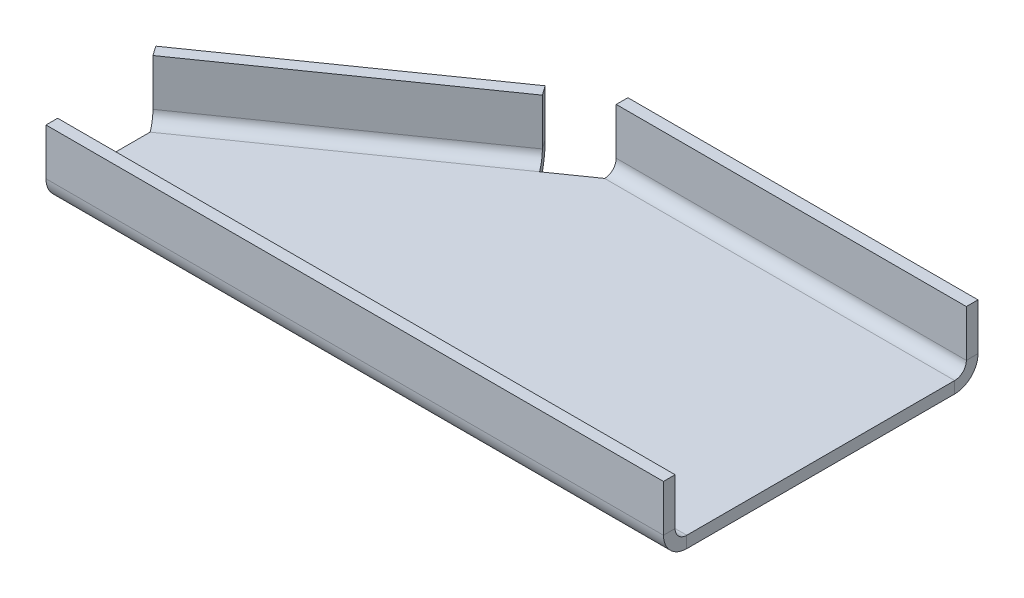
SolidWorks part; units mm, degrees
note: The reader was unsure of these and kept them because the rebuilt part matched: flange length of "Edge-Flange1".
material "5052-H32"
ref_plane "Front" through (0, 0, 0) normal (0, 0, 1) x (1, 0, 0)
ref_plane "Top" through (0, 0, 0) normal (0, 1, 0) x (1, 0, 0)
ref_plane "Right" through (0, 0, 0) normal (1, 0, 0) x (0, 0, -1)
sketch "Sketch1" plane through (0, 0, 0) normal (0, 1, 0) x (1, 0, 0)
  line L0 (0, 0) -> (168.275, 0) construction
  line L1 (168.275, 0) -> (168.275, 85.725) construction
  line L2 (168.275, 85.725) -> (73.025, 85.725) construction
  line L4 (0, 0) -> (0, 34.5923) construction
  line L5 (73.025, 85.725) -> (0, 34.5923) construction
  line L6 (168.275, 79.375) -> (72.8532, 79.375)
  line L7 (72.8532, 79.375) -> (0, 28.3626)
  line L8 (168.275, 79.375) -> (73.025, 79.375) construction
  line L9 (75.952, 81.5448) -> (2.927, 30.4121) construction
  line L13 (0, 6.35) -> (168.275, 6.35)
  line L14 (0, 28.3626) -> (0, 6.35)
  line L15 (168.275, 79.375) -> (168.275, 6.35)
  dimension "D1" = 95.25
  dimension "D2" = 168.275
  dimension "D3" = 85.725
  dimension "D4" = 35
  dimension "D7" = 12.7
  dimension "D5" = 6.35
  dimension "D6" = 5.1031
base flange "Base-Flange1" sketch "Sketch1" thickness 3.175 reverse thickness direction no parameters "D1"=6.35
edge flange "Edge-Flange1" sketch "Sketch12" flange profiles "Sketch12", "Sketch13", "Sketch14" flange angle 90 flange length 19.05 flange position bend outside bend radius 3.175 thickness 3.175 relief rectangular parameters "D6"=10, "D8"=1
sketch "Sketch12" plane through (0, 0, -79.375) normal (0, 0, -1) x (-1, 0, 0)
  line L0 (-168.275, 0) -> (-72.8532, 0) construction
  line L1 (-168.275, 0) -> (-72.8532, 0)
  line L2 (-168.275, 0) -> (-168.275, 15.875)
  line L3 (-168.275, 15.875) -> (-72.8532, 15.875)
  line L4 (-72.8532, 15.875) -> (-72.8532, 0)
sketch "Sketch13" plane through (0, 0, -6.35) normal (0, 0, 1) x (1, 0, 0)
  line L0 (0, 0) -> (168.275, 0) construction
  line L1 (0, 0) -> (168.275, 0)
  line L2 (0, 0) -> (0, 15.875)
  line L3 (0, 15.875) -> (168.275, 15.875)
  line L4 (168.275, 15.875) -> (168.275, 0)
sketch "Sketch14" plane through (-13.3261, 0, -19.0316) normal (-0.5736, 0, -0.8192) x (-0.8192, 0, 0.5736)
  line L0 (-105.2055, 0) -> (-16.2681, 0) construction
  line L1 (-92.4681, 0) -> (-16.2681, 0)
  line L2 (-92.4681, 0) -> (-92.4681, 15.875)
  line L3 (-92.4681, 15.875) -> (-16.2681, 15.875)
  line L4 (-16.2681, 15.875) -> (-16.2681, 0)
  dimension "D1" = 76.2
bend "EdgeBend1" bend radius 3.175 bend angle 90 parameters "D5"=1
bend "EdgeBend2" bend radius 3.175 bend angle 90 parameters "D5"=2
bend "EdgeBend3" bend radius 3.175 bend angle 90 parameters "D5"=3
sketch "Sketch15" plane through (0, 0, 0) normal (0, 0, 1) x (1, 0, 0)
  line L0 (0, -3.175) -> (168.275, -3.175) construction
  line L1 (168.275, 3.175) -> (168.275, 15.875) construction
  circle A0 centre (155.575, 9.525) radius 2.4257
  circle A1 centre (85.725, 9.525) radius 2.4257
  circle A2 centre (15.875, 9.525) radius 2.4257
  dimension "D3" = 4.8514
  dimension "D1" = 12.7
  dimension "D2" = 12.7
  dimension "D4" = 3
  dimension "D5" = 69.85
extrude "Cut-Extrude1" [suppressed] cut sketch "Sketch15" against normal up to surface (3.175 mm away)
sketch "Sketch16" plane through (0, 0, -85.725) normal (0, 0, -1) x (-1, 0, 0)
  line L0 (-120.5641, 15.875) -> (-120.5641, -3.175) construction
  line L1 (-72.8532, 15.875) -> (-168.275, 15.875) construction
  line L2 (-168.275, -3.175) -> (-72.8532, -3.175) construction
  circle A0 centre (-145.9641, 9.525) radius 2.4257
  circle A1 centre (-120.5641, 9.525) radius 2.4257 construction
  circle A2 centre (-95.1641, 9.525) radius 2.4257
  dimension "D2" = 4.8514
  dimension "D1" = 12.7
  dimension "D3" = 25.4
extrude "Cut-Extrude2" [suppressed] cut sketch "Sketch16" against normal up to surface (3.175 mm away)
sketch "Sketch17" plane through (-16.9683, 0, -24.2332) normal (-0.5736, 0, -0.8192) x (-0.8192, 0, 0.5736)
  line L0 (-54.3681, -3.175) -> (-54.3681, 15.875) construction
  line L1 (-16.2681, -3.175) -> (-92.4681, -3.175) construction
  line L2 (-16.2681, 15.875) -> (-92.4681, 15.875) construction
  circle A0 centre (-79.7681, 9.525) radius 2.4257
  circle A1 centre (-28.9681, 9.525) radius 2.4257
  dimension "D1" = 4.8514
  dimension "D2" = 12.7
  dimension "D3" = 25.4
extrude "Cut-Extrude3" [suppressed] cut sketch "Sketch17" against normal up to surface (3.175 mm away)
sketch "Sketch18" plane through (0, 0, 0) normal (0, 1, 0) x (1, 0, 0)
  line L0 (122.2375, 0) -> (122.2375, 35.7505) construction
  line L1 (122.2375, 35.7505) -> (168.275, 35.7505) construction
  line L2 (168.275, 6.35) -> (168.275, 79.375) construction
  line L3 (168.275, 0) -> (0, 0) construction
  circle A0 centre (122.2375, 35.7505) radius 17.4625
  dimension "D3" = 34.925
  dimension "D1" = 46.0375
  dimension "D2" = 35.7505
extrude "Cut-Extrude4" [suppressed] cut sketch "Sketch18" against normal through all
fillet "Fillet1" [suppressed] radius 3.175
sketch "Bend-Lines1" [suppressed] plane through (0, 0, 0) normal (0, 1, 0) x (1, 0, 0)
sketch "Bounding-Box1" [suppressed] plane through (0, 0, 0) normal (0, 1, 0) x (1, 0, 0)
sheet metal parameters "Sheet-Metal1" thickness 3.175 parameters "D1"=6.35
flat pattern "Flat-Pattern1" [suppressed]
sketch "Bend-Lines2" plane through (0, 0, 0) normal (0, 1, 0) x (1, 0, 0)
sketch3d "Bounding-Box2" [suppressed]
  line L0 (-168.275, 6.35, 0) -> (0, 6.35, 0) construction
  line L1 (-168.275, 79.375, 0) -> (0, 79.375, 0) construction
  line L2 (-168.275, 6.35, 0) -> (-168.275, 79.375, 0) construction
  line L3 (0, 6.35, 0) -> (0, 79.375, 0) construction
sheet metal parameters "Sheet-Metal2" thickness 3.175 parameters "D1"=6.35
flat pattern "Flat-Pattern1"
sketch "Bend-Lines2" plane through (0, 0, 0) normal (0, 1, 0) x (1, 0, 0)
  line L0 (60.7745, 74.4182) -> (-1.6448, 30.7117) construction
  line L1 (0, 3.4823) -> (168.275, 3.4823) construction
  line L2 (168.275, 82.2427) -> (72.8532, 82.2427) construction
  line L3 (60.7745, 74.4182) -> (-1.6448, 30.7117) construction
  line L4 (0, 3.4823) -> (168.275, 3.4823) construction
  line L5 (168.275, 82.2427) -> (72.8532, 82.2427) construction
sketch3d "Bounding-Box2" [suppressed]
  line L0 (168.275, -12.0854, 0) -> (-10.5741, -12.0854, 0) construction
  line L1 (168.275, 97.8104, 0) -> (-10.5741, 97.8104, 0) construction
  line L2 (168.275, -12.0854, 0) -> (168.275, 97.8104, 0) construction
  line L3 (-10.5741, -12.0854, 0) -> (-10.5741, 97.8104, 0) construction
bend of the flat pattern "Flatten-<EdgeBend1>1"
bend of the flat pattern "Flatten-<EdgeBend2>1"
bend of the flat pattern "Flatten-<EdgeBend3>1"
sheet metal parameters "Sheet-Metal3" thickness 3.175 parameters "D1"=6.35
flat pattern "Flat-Pattern1"
sketch "Bend-Lines2" plane through (0, 0, 0) normal (0, 1, 0) x (1, 0, 0)
  line L0 (60.7745, 74.4182) -> (-1.6448, 30.7117) construction
  line L1 (0, 3.4823) -> (168.275, 3.4823) construction
  line L2 (168.275, 82.2427) -> (72.8532, 82.2427) construction
  line L3 (60.7745, 74.4182) -> (-1.6448, 30.7117) construction
  line L4 (0, 3.4823) -> (168.275, 3.4823) construction
  line L5 (168.275, 82.2427) -> (72.8532, 82.2427) construction
sketch3d "Bounding-Box2" [suppressed]
  line L0 (168.275, -12.0854, 0) -> (-10.5741, -12.0854, 0) construction
  line L1 (168.275, 97.8104, 0) -> (-10.5741, 97.8104, 0) construction
  line L2 (168.275, -12.0854, 0) -> (168.275, 97.8104, 0) construction
  line L3 (-10.5741, -12.0854, 0) -> (-10.5741, 97.8104, 0) construction
bend of the flat pattern "Flatten-<EdgeBend1>1"
bend of the flat pattern "Flatten-<EdgeBend2>1"
bend of the flat pattern "Flatten-<EdgeBend3>1"
sheet metal parameters "Sheet-Metal4" thickness 3.175 parameters "D1"=6.35
flat pattern "Flat-Pattern1"
sketch "Bend-Lines2" plane through (0, 0, 0) normal (0, 1, 0) x (1, 0, 0)
  line L0 (60.7745, 74.4182) -> (-1.6448, 30.7117) construction
  line L1 (0, 3.4823) -> (168.275, 3.4823) construction
  line L2 (168.275, 82.2427) -> (72.8532, 82.2427) construction
  line L3 (60.7745, 74.4182) -> (-1.6448, 30.7117) construction
  line L4 (0, 3.4823) -> (168.275, 3.4823) construction
  line L5 (168.275, 82.2427) -> (72.8532, 82.2427) construction
sketch3d "Bounding-Box2" [suppressed]
  line L0 (168.275, -12.0854, 0) -> (-10.5741, -12.0854, 0) construction
  line L1 (168.275, 97.8104, 0) -> (-10.5741, 97.8104, 0) construction
  line L2 (168.275, -12.0854, 0) -> (168.275, 97.8104, 0) construction
  line L3 (-10.5741, -12.0854, 0) -> (-10.5741, 97.8104, 0) construction
bend of the flat pattern "Flatten-<EdgeBend1>1"
bend of the flat pattern "Flatten-<EdgeBend2>1"
bend of the flat pattern "Flatten-<EdgeBend3>1"
sheet metal parameters "Sheet-Metal5" thickness 3.175 parameters "D1"=6.35
flat pattern "Flat-Pattern1"
sketch "Bend-Lines2" plane through (0, 0, 0) normal (0, 1, 0) x (1, 0, 0)
  line L0 (60.7745, 74.4182) -> (-1.6448, 30.7117) construction
  line L1 (0, 3.4823) -> (168.275, 3.4823) construction
  line L2 (168.275, 82.2427) -> (72.8532, 82.2427) construction
  line L3 (60.7745, 74.4182) -> (-1.6448, 30.7117) construction
  line L4 (0, 3.4823) -> (168.275, 3.4823) construction
  line L5 (168.275, 82.2427) -> (72.8532, 82.2427) construction
sketch3d "Bounding-Box2" [suppressed]
  line L0 (168.275, -12.0854, 0) -> (-10.5741, -12.0854, 0) construction
  line L1 (168.275, 97.8104, 0) -> (-10.5741, 97.8104, 0) construction
  line L2 (168.275, -12.0854, 0) -> (168.275, 97.8104, 0) construction
  line L3 (-10.5741, -12.0854, 0) -> (-10.5741, 97.8104, 0) construction
bend of the flat pattern "Flatten-<EdgeBend1>1"
bend of the flat pattern "Flatten-<EdgeBend2>1"
bend of the flat pattern "Flatten-<EdgeBend3>1"
sheet metal parameters "Sheet-Metal6" thickness 3.175 parameters "D1"=6.35
flat pattern "Flat-Pattern1"
sketch "Bend-Lines2" plane through (0, 0, 0) normal (0, 1, 0) x (1, 0, 0)
  line L0 (60.7745, 74.4182) -> (-1.6448, 30.7117) construction
  line L1 (0, 3.4823) -> (168.275, 3.4823) construction
  line L2 (168.275, 82.2427) -> (72.8532, 82.2427) construction
  line L3 (60.7745, 74.4182) -> (-1.6448, 30.7117) construction
  line L4 (0, 3.4823) -> (168.275, 3.4823) construction
  line L5 (168.275, 82.2427) -> (72.8532, 82.2427) construction
sketch3d "Bounding-Box2" [suppressed]
  line L0 (168.275, -12.0854, 0) -> (-10.5741, -12.0854, 0) construction
  line L1 (168.275, 97.8104, 0) -> (-10.5741, 97.8104, 0) construction
  line L2 (168.275, -12.0854, 0) -> (168.275, 97.8104, 0) construction
  line L3 (-10.5741, -12.0854, 0) -> (-10.5741, 97.8104, 0) construction
bend of the flat pattern "Flatten-<EdgeBend1>1"
bend of the flat pattern "Flatten-<EdgeBend2>1"
bend of the flat pattern "Flatten-<EdgeBend3>1"
